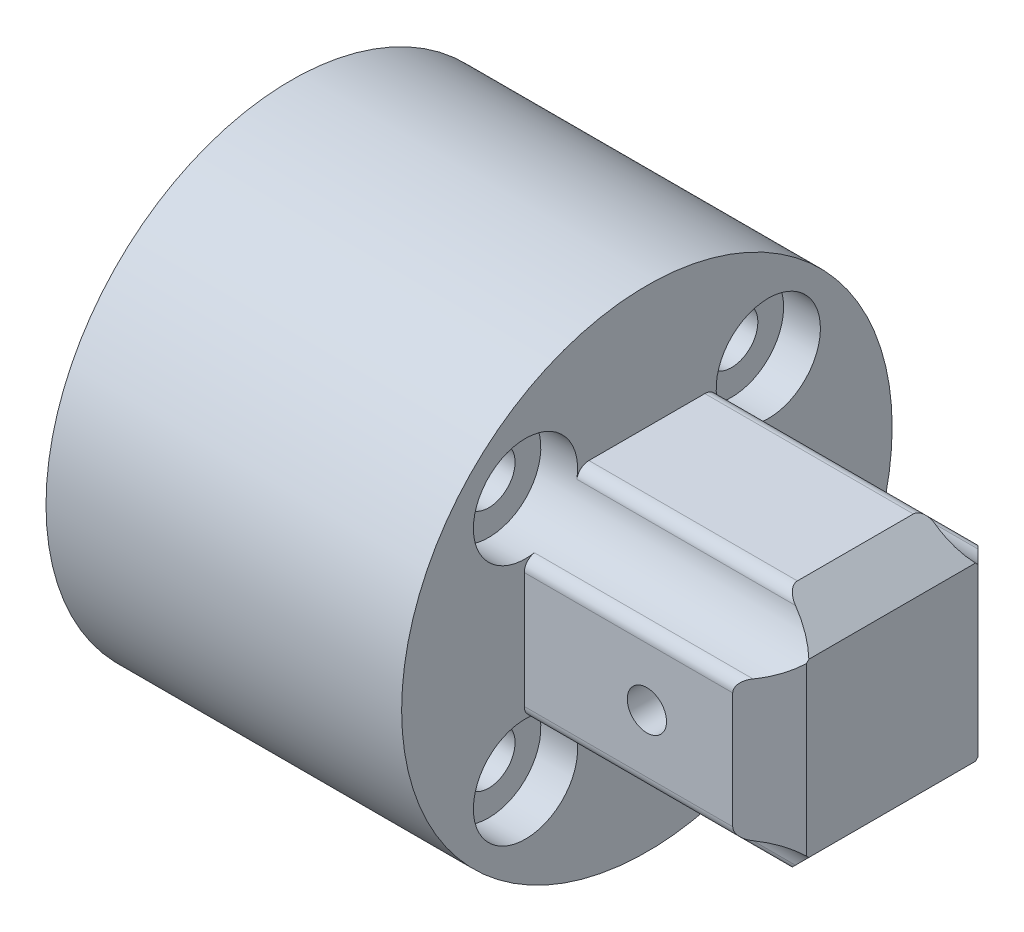
SolidWorks part; units mm, degrees
ref_plane "前视基准面" through (0, 0, 0) normal (0, 0, 1) x (1, 0, 0)
ref_plane "上视基准面" through (0, 0, 0) normal (0, 1, 0) x (1, 0, 0)
ref_plane "右视基准面" through (0, 0, 0) normal (1, 0, 0) x (0, 0, -1)
sketch "草图1" plane through (0, 0, 0) normal (1, 0, 0) x (0, 0, -1)
  circle A0 centre (0, 0) radius 20
  dimension "D1" = 40
extrude "凸台-拉伸1" add sketch "草图1" along normal blind 10
sketch "草图2" plane through (0, 0, 0) normal (-1, 0, 0) x (0, 0, 1)
  line L1 (-7.5, -15.25) -> (7.5, -15.25)
  line L2 (-7.5, -15.25) -> (-7.5, 15.25)
  line L3 (-7.5, 15.25) -> (7.5, 15.25)
  line L4 (7.5, -15.25) -> (7.5, 15.25)
  line L5 (-7.5, -15.25) -> (7.5, 15.25) construction
  line L6 (-7.5, 15.25) -> (7.5, -15.25) construction
  point P0 (0, 0)
  dimension "D1" = 15
  dimension "D2" = 30.5
extrude "切除-拉伸1" cut sketch "草图2" against normal blind 4
sketch "草图3" plane through (4, 0, 0) normal (-1, 0, 0) x (0, 0, 1)
  circle A0 centre (0, 0) radius 8.75
  dimension "D1" = 17.5
extrude "切除-拉伸2" cut sketch "草图3" along normal blind 4
sketch "草图4" plane through (0, 0, 0) normal (-1, 0, 0) x (0, 0, 1)
  line L1 (-9, -16) -> (9, -16)
  line L2 (-9, -16) -> (-9, 16)
  line L3 (-9, 16) -> (9, 16)
  line L4 (9, -16) -> (9, 16)
  line L5 (-9, -16) -> (9, 16) construction
  line L6 (-9, 16) -> (9, -16) construction
  circle A0 centre (0, 0) radius 20
  dimension "D3" = 40
  dimension "D1" = 32
  dimension "D2" = 18
extrude "凸台-拉伸2" add sketch "草图4" along normal blind 19
fillet "圆角1" radius 3 4 edges at (-9.5, -16, -9) (-9.5, -16, 9) (-9.5, 16, -9) (-9.5, 16, 9)
sketch "草图5" plane through (-19, 0, 0) normal (-1, 0, 0) x (0, 0, 1)
  line L0 (-6, -16) -> (6, -16) construction
  line L1 (6, 16) -> (-6, 16) construction
  circle A0 centre (0, -16) radius 2.5
  circle A1 centre (0, 16) radius 2.5
  dimension "D1" = 5
  dimension "D2" = 5
extrude "切除-拉伸3" cut sketch "草图5" against normal blind 20
fillet "圆角2" radius 3 4 edges at (-9.5, -16, -2.5) (-9.5, -16, 2.5) (-9.5, 16, 2.5) (-9.5, 16, -2.5)
sketch "草图6" plane through (10, 0, 0) normal (1, 0, 0) x (0, 0, -1)
  line L0 (0, 0) -> (20, 0) construction
  line L1 (0, 0) -> (18.216, -18.216) construction
  circle A0 centre (0, 0) radius 14 construction
  circle A2 centre (9.8995, -9.8995) radius 2.15
  circle A3 centre (0, 0) radius 14 construction
  circle A4 centre (-9.8995, -9.8995) radius 2.15
  circle A5 centre (0, 0) radius 14 construction
  circle A6 centre (-9.8995, 9.8995) radius 2.15
  circle A7 centre (0, 0) radius 14 construction
  circle A8 centre (9.8995, 9.8995) radius 2.15
  point P21 (0, 0)
  dimension "D1" = 28
  dimension "D3" = 4.3
  dimension "D2" = 45
  dimension "D4" = 4
extrude "切除-拉伸4" cut sketch "草图6" against normal blind 43
fillet "圆角3" radius 1 8 edges at (-9.5, -7.9467, 9) (-9.5, -11.8523, 9) (-9.5, -11.8523, -9) (-9.5, -7.9467, -9) (-9.5, 7.9467, -9) (-9.5, 11.8523, -9) (-9.5, 11.8523, 9) (-9.5, 7.9467, 9)
sketch "草图7" plane through (10, 0, 0) normal (1, 0, 0) x (0, 0, -1)
  circle A0 centre (9.8995, -9.8995) radius 4.25
  dimension "D1" = 8.5
extrude "切除-拉伸5" cut sketch "草图7" against normal blind 3
pattern_circular "阵列(圆周)1" count 4 over 360 about axis through (0, 0, 0) along (1, 0, 0) of "切除-拉伸5"
sketch "草图8" plane through (10, 0, 0) normal (1, 0, 0) x (0, 0, -1)
  line L1 (-10, -10) -> (10, -10)
  line L2 (-10, -10) -> (-10, 10)
  line L3 (-10, 10) -> (10, 10)
  line L4 (10, -10) -> (10, 10)
  line L5 (-10, -10) -> (10, 10) construction
  line L6 (-10, 10) -> (10, -10) construction
  point P0 (0, 0)
  dimension "D1" = 20
  dimension "D2" = 20
extrude "凸台-拉伸3" add sketch "草图8" along normal blind 20
sketch "草图9" plane through (0, 0, -10) normal (0, 0, -1) x (-1, 0, 0)
  line L0 (-10, 20) -> (-10, -20) construction
  circle A0 centre (-20, 0) radius 1.6
  dimension "D1" = 3.2
  dimension "D2" = 10
extrude "切除-拉伸6" cut sketch "草图9" against normal blind 27
chamfer "倒角1" distance 3 angle 45 4 edges at (30, -10, 0) (30, 0, 10) (30, 10, 0) (30, 0, -10)
sketch "草图11" plane through (10, 0, 0) normal (1, 0, 0) x (0, 0, -1)
  circle A0 centre (-9.8995, 9.8995) radius 4.25
  circle A1 centre (-9.8995, -9.8995) radius 4.25
  circle A2 centre (9.8995, -9.8995) radius 4.25
  circle A3 centre (9.8995, 9.8995) radius 4.25
  point P12 (0, 0)
  dimension "D1" = 8.5
  dimension "D2" = 4
extrude "切除-拉伸7" cut sketch "草图11" along normal blind 49
sketch "草图12" plane through (0, -15.25, 0) normal (0, 1, 0) x (1, 0, 0)
  line L1 (1.5, -2.5) -> (-1.5, -2.5)
  line L2 (1.5, -2.5) -> (1.5, 2.5)
  line L3 (1.5, 2.5) -> (-1.5, 2.5)
  line L4 (-1.5, -2.5) -> (-1.5, 2.5)
  line L5 (1.5, -2.5) -> (-1.5, 2.5) construction
  line L6 (1.5, 2.5) -> (-1.5, -2.5) construction
  point P0 (0, 0)
  dimension "D1" = 3
  dimension "D2" = 5
extrude "切除-拉伸8" cut sketch "草图12" against normal blind 49
fillet "圆角4" radius 1 3 edges at (0.75, -15.25, 2.5) (0.75, -15.25, -2.5) (1.5, -15.25, 0)
fillet "圆角5" radius 1 4 edges at (0, -19.8431, 2.5) (1.5, -20, 0) (0, -19.8431, -2.5) (-1.5, -20, 0)
fillet "圆角6" radius 1 11 edges at (28.6119, -8.3881, -5.9273) (28.6119, 5.9273, -8.3881) (18.5, 10, -5.6507) (18.5, 5.6507, -10) (18.5, -10, -5.6507) (28.6119, -5.9273, 8.3881) (18.5, -5.6507, 10) (18.5, -10, 5.6507) (28.6119, 8.3881, 5.9273) (18.5, 10, 5.6507) (18.5, 5.6507, 10)
fillet "圆角7" radius 1 1 edges at (18.5, -5.6507, -10)
sketch "草图13" plane through (0, 0, 0) normal (0, 1, 0) x (1, 0, 0)
  line L1 (-8, -7.5) -> (5, -7.5)
  line L2 (-8, -7.5) -> (-8, 7.5)
  line L3 (-8, 7.5) -> (5, 7.5)
  line L4 (5, -7.5) -> (5, 7.5)
  dimension "D1" = 15
  dimension "D2" = 13
  dimension "D3" = 5
  dimension "D4" = 7.5
extrude "切除-拉伸9" cut sketch "草图13" against normal blind 28
fillet "圆角8" radius 3 4 edges at (5, -9.2702, -7.5) (-8, -17.0693, -7.5) (-8, -17.0693, 7.5) (5, -9.2702, 7.5)
sketch "草图14" plane through (10, 0, 0) normal (1, 0, 0) x (0, 0, -1)
  line L1 (-15.2909, -19.7) -> (15.7365, -19.7)
  line L2 (-15.2909, -19.7) -> (-15.2909, -22.5409)
  line L3 (-15.2909, -22.5409) -> (15.7365, -22.5409)
  line L4 (15.7365, -19.7) -> (15.7365, -22.5409)
  dimension "D1" = 19.7
extrude "切除-拉伸10" [suppressed] cut sketch "草图14" against normal blind 7
sketch "草图15" [suppressed] plane through (0, -19.7, 0) normal (0, -1, 0) x (1, 0, 0)
  line L0 (10, -3.4511) -> (10, 3.4511) construction
  line L1 (10, 2.9989) -> (3, 2.9989)
  line L2 (10, 2.9989) -> (10, -3.0011)
  line L3 (10, -3.0011) -> (3, -3.0011)
  line L4 (3, 2.9989) -> (3, -3.0011)
  line L5 (3, -2) -> (3, 2) construction
  line L6 (10, -3.4511) -> (3, -3.4511) construction
  line L7 (3, 3.4511) -> (10, 3.4511) construction
  dimension "D1" = 6
  dimension "D2" = 0.45
  dimension "D3" = 0.4522
extrude "凸台-拉伸4" [suppressed] add sketch "草图15" along normal blind 10
sketch "草图16" [suppressed] plane through (3, 0, 0) normal (-1, 0, 0) x (0, 0, 1)
  line L0 (-3.0011, -29.7) -> (-3.0011, -19.7736) construction
  line L1 (-3.0011, -26.7) -> (2.9989, -26.7)
  line L2 (-3.0011, -26.7) -> (-3.0011, -32.7)
  line L3 (-3.0011, -32.7) -> (2.9989, -32.7)
  line L4 (2.9989, -26.7) -> (2.9989, -32.7)
  line L5 (2.9989, -29.7) -> (-3.0011, -29.7) construction
  dimension "D1" = 6
  dimension "D2" = 3
  dimension "D3" = 6
extrude "凸台-拉伸5" [suppressed] add sketch "草图16" along normal blind 6
sketch "草图17" [suppressed] plane through (0, -32.7, 0) normal (0, -1, 0) x (1, 0, 0)
  circle A0 centre (0, 0) radius 1.2
  dimension "D1" = 2.4
extrude "切除-拉伸11" [suppressed] cut sketch "草图17" against normal blind 10
sketch "草图18" [suppressed] plane through (-3, 0, 0) normal (-1, 0, 0) x (0, 0, 1)
  line L0 (2.9989, -32.7) -> (2.9989, -26.7) construction
  line L1 (0.4989, -34.3413) -> (-0.5011, -34.3413)
  line L2 (0.4989, -34.3413) -> (0.4989, -25.4298)
  line L3 (0.4989, -25.4298) -> (-0.5011, -25.4298)
  line L4 (-0.5011, -34.3413) -> (-0.5011, -25.4298)
  line L5 (0.4989, -34.3413) -> (-0.5011, -25.4298) construction
  line L6 (0.4989, -25.4298) -> (-0.5011, -34.3413) construction
  point P0 (-0.0011, -29.8855)
  dimension "D1" = 1
  dimension "D2" = 2.5
extrude "切除-拉伸12" [suppressed] cut sketch "草图18" against normal blind 5
sketch "草图19" [suppressed] plane through (-3, 0, 0) normal (-1, 0, 0) x (0, 0, 1)
  line L0 (0.4989, -32.7) -> (2.9989, -32.7) construction
  line L1 (0.4989, -26.7) -> (2.9989, -26.7)
  line L2 (0.4989, -26.7) -> (0.4989, -32.7)
  line L3 (0.4989, -32.7) -> (2.9989, -32.7)
  line L4 (2.9989, -26.7) -> (2.9989, -32.7)
  line L5 (-3.0011, -32.7) -> (-0.5011, -32.7) construction
  line L6 (-0.5011, -26.7) -> (-3.0011, -26.7)
  line L7 (-0.5011, -26.7) -> (-0.5011, -32.7)
  line L8 (-0.5011, -32.7) -> (-3.0011, -32.7)
  line L9 (-3.0011, -26.7) -> (-3.0011, -32.7)
  dimension "D1" = 2.5
  dimension "D2" = 2.5
extrude "凸台-拉伸6" [suppressed] add sketch "草图19" along normal blind 3
sketch "草图20" [suppressed] plane through (0, 0, -3.0011) normal (0, 0, -1) x (-1, 0, 0)
  line L0 (6, -26.7) -> (6, -32.7) construction
  circle A0 centre (3.5, -29.7) radius 1.7
  dimension "D1" = 3.4
  dimension "D2" = 2.5
extrude "切除-拉伸13" [suppressed] cut sketch "草图20" against normal blind 3
sketch "草图21" [suppressed] plane through (0, 0, 0.4989) normal (0, 0, -1) x (-1, 0, 0)
  circle A0 centre (3.5, -29.7) radius 1
  dimension "D1" = 2
extrude "切除-拉伸14" [suppressed] cut sketch "草图21" against normal blind 3
chamfer "倒角2" [suppressed] distance 5 angle 45
chamfer "倒角3" [suppressed] distance 2 angle 45
sketch "草图22" [suppressed] plane through (-6, 0, 0) normal (-1, 0, 0) x (0, 0, 1)
  line L0 (2.9989, -26.7) -> (0.6633, -26.7) construction
  line L1 (-0.6633, -32.7) -> (0.6633, -32.7)
  line L2 (-0.6633, -32.7) -> (-0.6633, -26.7)
  line L3 (-0.6633, -26.7) -> (0.6633, -26.7)
  line L4 (0.6633, -32.7) -> (0.6633, -26.7)
  line L5 (-0.6633, -32.7) -> (0.6633, -26.7) construction
  line L6 (-0.6633, -26.7) -> (0.6633, -32.7) construction
  line L7 (2.9989, -26.7) -> (0.4989, -26.7) construction
  point P0 (0, -29.7)
extrude "切除-拉伸15" [suppressed] cut sketch "草图22" against normal blind 5
sketch "草图23" [suppressed] plane through (0, 0, -3.0011) normal (0, 0, -1) x (-1, 0, 0)
  line L0 (-10, -19.7) -> (-5, -32.7)
  line L1 (-5, -32.7) -> (-10, -29.7)
  line L2 (-10, -29.7) -> (-10, -19.7)
extrude "切除-拉伸16" [suppressed] cut sketch "草图23" against normal blind 9
sketch "草图24" [suppressed] plane through (0, 0, -3.0011) normal (0, 0, -1) x (-1, 0, 0)
  line L0 (-10, -19.7) -> (-3.5, -32.7)
  line L1 (6, -32.7) -> (-5, -32.7) construction
  line L2 (-3.5, -32.7) -> (-5, -32.7)
  line L3 (-5, -32.7) -> (-10, -19.7)
  dimension "D1" = 1.5
extrude "切除-拉伸17" [suppressed] cut sketch "草图24" against normal blind 9
sketch "草图25" [suppressed] plane through (-6, 0, 0) normal (-1, 0, 0) x (0, 0, 1)
  line L1 (-5.601, -24.3975) -> (10.1119, -24.3975)
  line L2 (-5.601, -24.3975) -> (-5.601, -35.5995)
  line L3 (-5.601, -35.5995) -> (10.1119, -35.5995)
  line L4 (10.1119, -24.3975) -> (10.1119, -35.5995)
extrude "切除-拉伸18" [suppressed] cut sketch "草图25" against normal blind 9
sketch "草图26" [suppressed] plane through (3, 0, 0) normal (-1, 0, 0) x (0, 0, 1)
  line L0 (-3.0011, -32.7) -> (-3.0011, -19.7736) construction
  line L1 (-3.0011, -26.7) -> (2.9989, -26.7)
  line L2 (-3.0011, -26.7) -> (-3.0011, -32.7)
  line L3 (-3.0011, -32.7) -> (2.9989, -32.7)
  line L4 (2.9989, -26.7) -> (2.9989, -32.7)
  dimension "D1" = 6
extrude "凸台-拉伸7" [suppressed] add sketch "草图26" along normal blind 5
sketch "草图27" [suppressed] plane through (0, -32.7, 0) normal (0, -1, 0) x (1, 0, 0)
  line L0 (-2, -3.0011) -> (-2, 2.9989) construction
  circle A0 centre (-2, -0.0011) radius 2
extrude "切除-拉伸19" [suppressed] cut sketch "草图27" against normal blind 8
sketch "草图28" [suppressed] plane through (-2, 0, 0) normal (-1, 0, 0) x (0, 0, 1)
  line L0 (2.9989, -26.7) -> (-3.0011, -26.7) construction
  line L1 (-1.5011, -26.7) -> (1.4989, -26.7)
  line L2 (-1.5011, -26.7) -> (-1.5011, -32.7)
  line L3 (-1.5011, -32.7) -> (1.4989, -32.7)
  line L4 (1.4989, -26.7) -> (1.4989, -32.7)
  line L5 (-3.0011, -32.7) -> (2.9989, -32.7) construction
  line L6 (-3.0011, -26.7) -> (-3.0011, -32.7) construction
  dimension "D1" = 3
  dimension "D2" = 1.5
extrude "切除-拉伸20" [suppressed] cut sketch "草图28" against normal blind 4
sketch "草图29" [suppressed] plane through (0, 0, 2.9989) normal (0, 0, 1) x (1, 0, 0)
  line L1 (-2, -26.7) -> (3.5, -26.7)
  line L2 (-2, -26.7) -> (-2, -32.7)
  line L3 (-2, -32.7) -> (3.5, -32.7)
  line L4 (3.5, -26.7) -> (3.5, -32.7)
extrude "凸台-拉伸8" [suppressed] add sketch "草图29" along normal blind 2
sketch "草图30" [suppressed] plane through (0, 0, -3.0011) normal (0, 0, -1) x (-1, 0, 0)
  line L1 (2, -26.7) -> (-3.5, -26.7)
  line L2 (2, -26.7) -> (2, -32.7)
  line L3 (2, -32.7) -> (-3.5, -32.7)
  line L4 (-3.5, -26.7) -> (-3.5, -32.7)
extrude "凸台-拉伸9" [suppressed] add sketch "草图30" along normal blind 2
chamfer "倒角4" [suppressed] distance 2 angle 45
chamfer "倒角5" [suppressed] distance 2 angle 45
chamfer "倒角6" [suppressed] distance 2 angle 45
fillet "圆角9" [suppressed] radius 2
sketch "草图31" plane through (5, 0, 0) normal (-1, 0, 0) x (0, 0, 1)
  line L0 (-7.5, -4.5069) -> (-7.5, -15.5981) construction
  line L1 (-7.5, -13) -> (7.5, -13)
  line L2 (-7.5, -13) -> (-7.5, 0.9203)
  line L3 (-7.5, 0.9203) -> (7.5, 0.9203)
  line L4 (7.5, -13) -> (7.5, 0.9203)
  line L5 (6.7361, 0) -> (-6.7361, 0) construction
  dimension "D1" = 15
  dimension "D2" = 13
extrude "凸台-拉伸10" add sketch "草图31" along normal blind 1
chamfer "倒角7" distance 1 angle 45 1 edges at (4, -13, 0)
